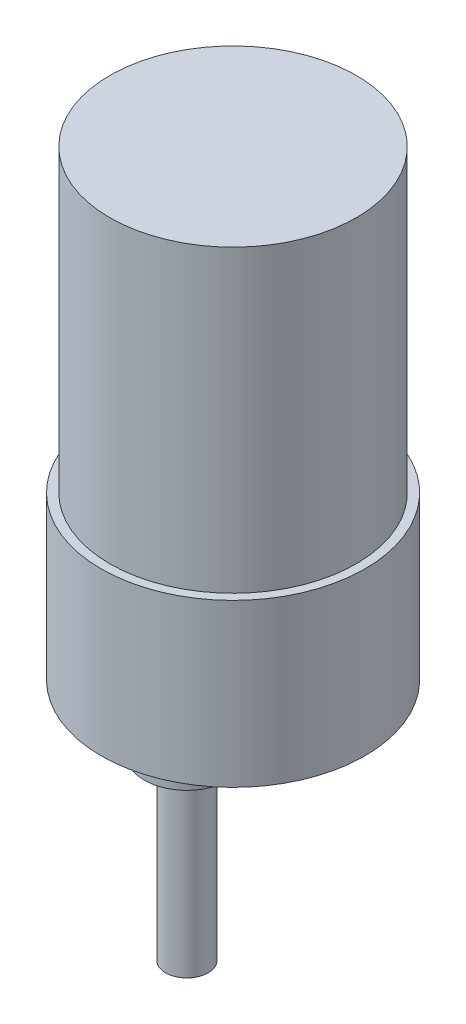
SolidWorks part; units mm, degrees
ref_plane "前视基准面" through (0, 0, 0) normal (0, 0, 1) x (1, 0, 0)
ref_plane "上视基准面" through (0, 0, 0) normal (0, 1, 0) x (1, 0, 0)
ref_plane "右视基准面" through (0, 0, 0) normal (1, 0, 0) x (0, 0, -1)
sketch "草图1" plane through (0, 0, 0) normal (0, 1, 0) x (1, 0, 0)
  circle A0 centre (0, 0) radius 18.575
  circle A1 centre (0, 0) radius 17.35
  dimension "D1" = 37.15
  dimension "D2" = 34.7
extrude "gear box" add sketch "草图1" along normal blind 22.8 contours A0
extrude "motor" add sketch "草图1<3>" along normal blind 65 contours A1
sketch "草图1<3>" plane through (0, 0, 0) normal (0, 1, 0) x (1, 0, 0) same geometry as "草图1"
sketch "草图2" plane through (0, 0, 0) normal (0, -1, 0) x (1, 0, 0)
  line L0 (-22.2069, 0) -> (22.999, 0) construction
  line L1 (0, 20.5661) -> (0, -20.5661) construction
  circle A0 centre (0, 6.5) radius 6
  circle A1 centre (0, 6.5) radius 3
  circle A2 centre (14, 0) radius 1
  circle A3 centre (-14, 0) radius 1
  dimension "D1" = 12
  dimension "D2" = 6
  dimension "D4" = 14
  dimension "D3" = 6.5
extrude "Cu bearing" add sketch "草图2" along normal blind 6 contours A0 A1 region at (-5.8303, 0, 6.5)
extrude "6mmshaft" add sketch "草图2<3>" along normal blind 31 contours A1 region at (0, 0, 6.5)
sketch "草图2<3>" plane through (0, 0, 0) normal (0, -1, 0) x (1, 0, 0) same geometry as "草图2"
extrude "M2 tapping hole" cut sketch "草图2<4>" against normal blind 5 contours A3 | A2 region at (14, 0, 0) region at (-14, 0, 0)
sketch "草图2<4>" plane through (0, 0, 0) normal (0, -1, 0) x (1, 0, 0) same geometry as "草图2"
